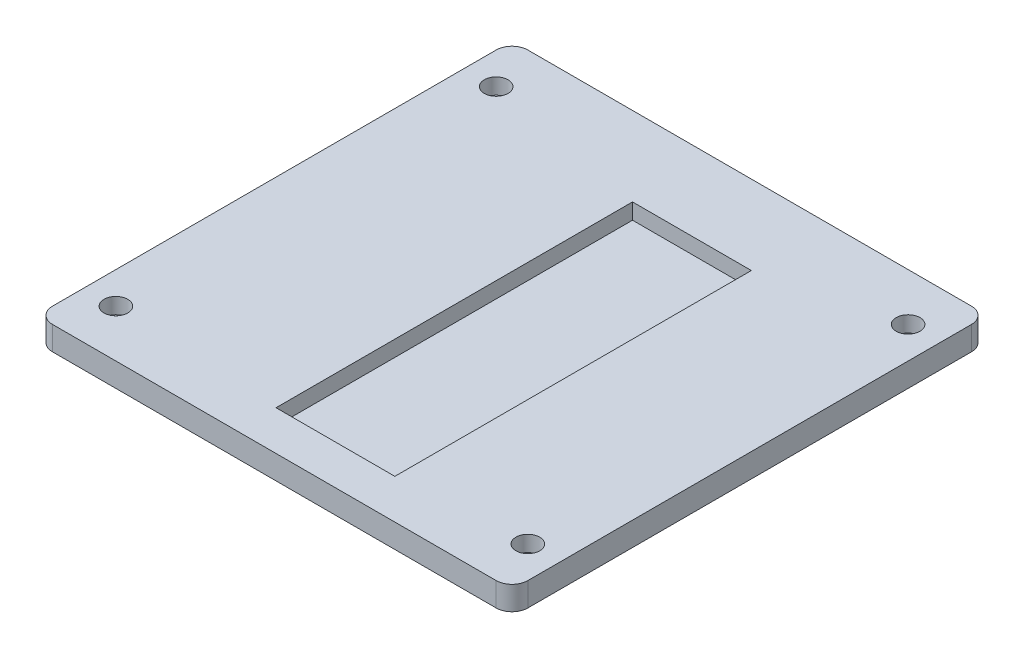
SolidWorks part; units mm, degrees
ref_plane "Alzado" through (0, 0, 0) normal (0, 0, 1) x (1, 0, 0)
ref_plane "Planta" through (0, 0, 0) normal (0, 1, 0) x (1, 0, 0)
ref_plane "Vista lateral" through (0, 0, 0) normal (1, 0, 0) x (0, 0, -1)
sketch "Croquis9" plane through (0, 0, 0) normal (0, 0, 1) x (1, 0, 0)
  line L0 (0, 17.7123) -> (0, -23.4478) construction
  line L1 (0, 10.708) -> (-22, 10.708)
  line L2 (-22, 10.708) -> (-22, 7.708)
  line L3 (-22, 7.708) -> (-13.4884, 7.708)
  line L4 (-13.4884, 7.708) -> (-4.5, 6.708)
  line L5 (-4.5, 6.708) -> (-4.5, -1.292)
  line L6 (-4.5, -1.292) -> (0, -1.292)
  line L7 (0, 10.708) -> (0, -1.292)
  dimension "D1" = 22
  dimension "D2" = 4.5
  dimension "D3" = 3
  dimension "D4" = 1
  dimension "D5" = 8
revolve "Revolución3" add sketch "Croquis9" angle 360 about L0
sketch "Croquis17" plane through (0, 0, 0) normal (1, 0, 0) x (0, 0, -1)
  line L0 (-4.5, -1.292) -> (4.5, -1.292) construction
  circle A0 centre (0, 4.708) radius 1.5
  dimension "D1" = 3
  dimension "D2" = 6
extrude "Cortar-Extruir7" cut sketch "Croquis17" along normal up to next
sketch "Croquis18" plane through (0, 10.708, 0) normal (0, 1, 0) x (1, 0, 0)
  line L0 (1, 2.9343) -> (1, -2.9343)
  arc A0 (1, 2.9343) -> (1, -2.9343) centre (0, 0) ccw
  dimension "D1" = 6.2
  dimension "D2" = 1
extrude "Cortar-Extruir10" cut sketch "Croquis18" against normal blind 6 from offset 3 offset against normal yes
sketch "Croquis21" plane through (0, 0, 0) normal (0, 0, 1) x (1, 0, 0)
  line L0 (0, 3.5811) -> (0, -1.3759) construction
  line L1 (0, 1.8085) -> (-3.1, 1.8085)
  line L2 (-3.1, 1.8085) -> (-3.1, -1.6716)
  line L3 (-3.1, -1.6716) -> (0, -1.6716)
  line L4 (0, 1.8085) -> (0, -1.6716)
  dimension "D1" = 3.1
revolve "Cortar-Revolución1" cut sketch "Croquis21" angle 360 about L0
chamfer "Chaflán2" distance 0.5 angle 45 1 edges at (1, 1.8085, 0)
chamfer "Chaflán1" [suppressed] distance 0.5 angle 45
sketch "Croquis22" plane through (0, 10.708, 0) normal (0, 1, 0) x (1, 0, 0)
  line L1 (-30, -30) -> (30, -30)
  line L2 (-30, -30) -> (-30, 30)
  line L3 (-30, 30) -> (30, 30)
  line L4 (30, -30) -> (30, 30)
  line L5 (-30, -30) -> (30, 30) construction
  line L6 (-30, 30) -> (30, -30) construction
  point P0 (0, 0)
  dimension "D1" = 60
  dimension "D2" = 60
extrude "Saliente-Extruir1" add sketch "Croquis22" against normal up to surface (3 mm away) up to face at (0, 7.708, 13.4884)
fillet "Redondeo1" radius 2 4 edges at (-30, 9.208, -30) (30, 9.208, -30) (30, 9.208, 30) (-30, 9.208, 30)
sketch "Croquis23" plane through (0, 10.708, 0) normal (0, 1, 0) x (1, 0, 0)
  line L0 (-30, 28) -> (-30, -28) construction
  line L1 (30, -28) -> (30, 28) construction
  line L2 (-28, -30) -> (28, -30) construction
  line L3 (-4.7864, 20) -> (10.2136, 20)
  line L4 (-4.7864, 20) -> (-4.7864, -25)
  line L5 (-4.7864, -25) -> (10.2136, -25)
  line L6 (10.2136, 20) -> (10.2136, -25)
  circle A0 centre (-26, 24) radius 1.5
  circle A1 centre (-26, -24) radius 1.5
  circle A2 centre (26, -24) radius 1.5
  circle A3 centre (26, 24) radius 1.5
  dimension "D1" = 3
  dimension "D4" = 24
  dimension "D6" = 15
  dimension "D8" = 5
  dimension "D2" = 4
  dimension "D3" = 4
  dimension "D5" = 48
  dimension "D7" = 45
extrude "Cortar-Extruir11" cut sketch "Croquis23" against normal blind 2
